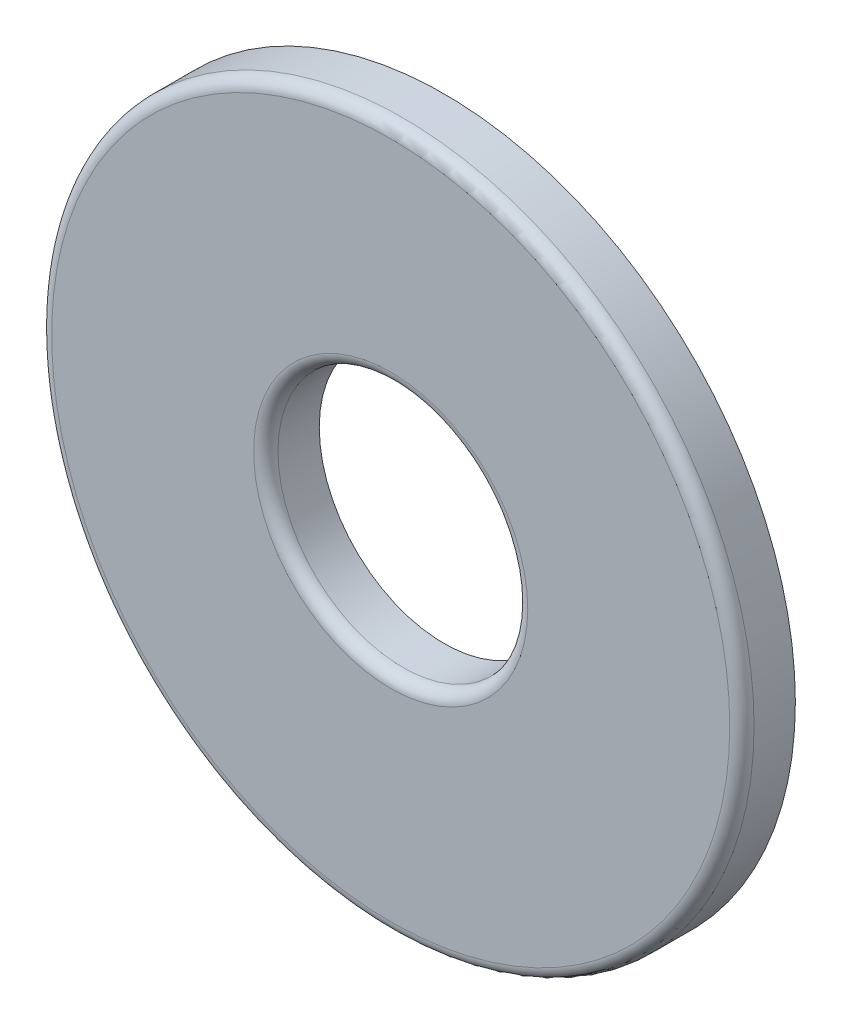
SolidWorks part; units mm, degrees
material "Stainless Steel (ferritic)"
ref_plane "Front Plane" through (0, 0, 0) normal (1, 0, 0) x (0, 1, 0)
ref_plane "Top Plane" through (0, 0, 0) normal (0, 0, 1) x (0, 1, 0)
ref_plane "Right Plane" through (0, 0, 0) normal (0, 1, 0) x (-1, 0, 0)
sketch "Sketch1" plane through (0, 0, 0) normal (0, 0, 1) x (0, 1, 0)
  circle A0 centre (0, 0) radius 6.5278
  circle A1 centre (0, 0) radius 18.3515
  dimension "D1" = 13.0556
  dimension "D2" = 36.703
extrude "Boss-Extrude1" add sketch "Sketch1" along normal blind 2.794
fillet "Fillet1" radius 0.635 2 edges at (6.5278, 0, 2.794) (18.3515, 0, 2.794)
